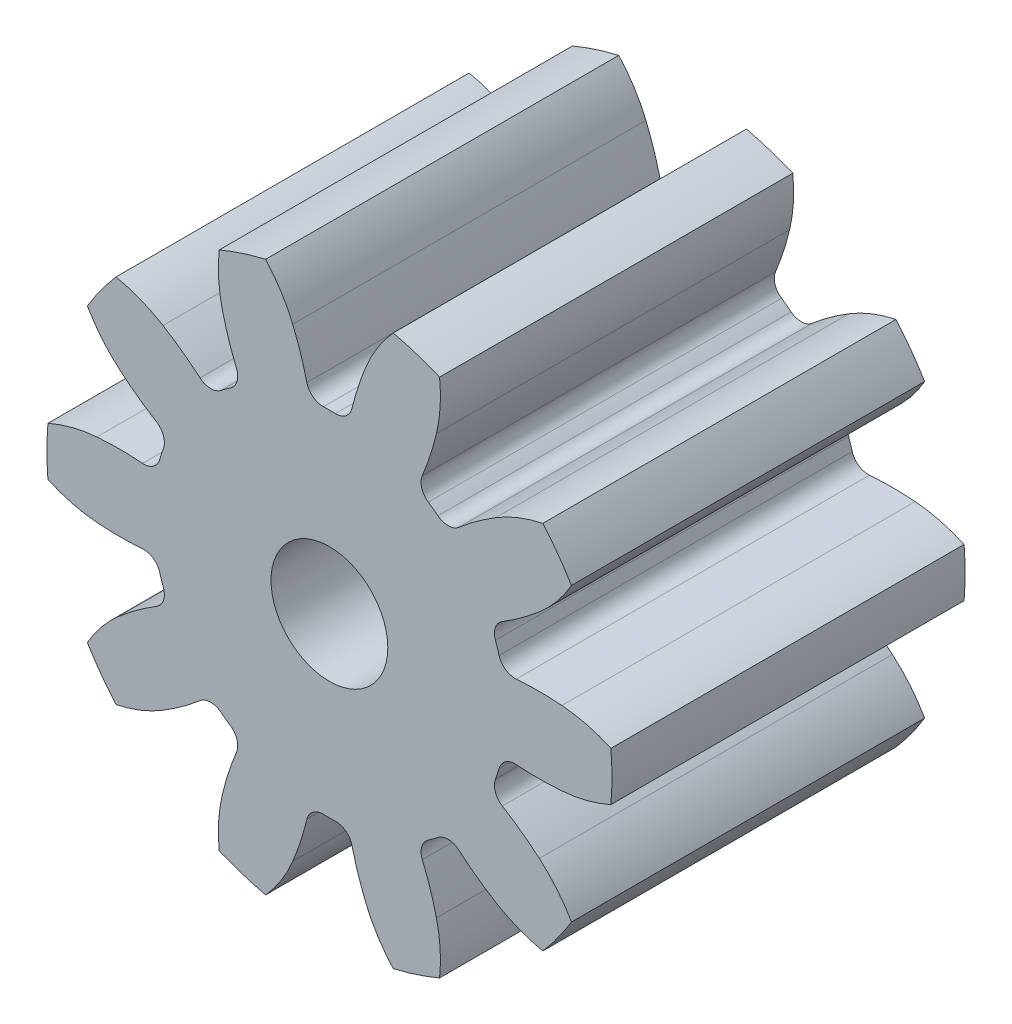
SolidWorks part; units mm, degrees
material "Alum Plate"
ref_plane "Front" through (0, 0, 0) normal (0, 0, 1) x (1, 0, 0)
ref_plane "Top" through (0, 0, 0) normal (0, 1, 0) x (1, 0, 0)
ref_plane "Right" through (0, 0, 0) normal (1, 0, 0) x (0, 0, -1)
sketch "Sketch1" plane through (0, 0, 0) normal (0, 0, 1) x (1, 0, 0)
  line L0 (0, 0) -> (6.35, 0) construction
  line L1 (6.35, 0) -> (7.62, 0) construction
  circle A0 centre (0, 0) radius 6.35 construction
  circle A1 centre (0, 0) radius 7.62
  dimension "D1" = 12.7
  dimension "D2" = 1.27
extrude "Round Stock" add sketch "Sketch1" along normal mid plane 9.525
sketch "Sketch2" plane through (0, 0, 4.7625) normal (0, 0, 1) x (1, 0, 0)
  line L0 (0, 0) -> (4.7625, 0) construction
  line L1 (4.7625, 0) -> (6.35, 0) construction
  line L2 (0, 0) -> (-7.62, 0) construction
  line L3 (0, 0) -> (-6.1647, -4.4789) construction
  line L4 (-6.5279, -3.9307) -> (-5.6598, -2.879) construction
  line L5 (-5.6598, -2.879) -> (-4.3534, -1.9312) construction
  line L6 (-7.5916, -0.657) -> (-6.2712, -0.9976) construction
  line L7 (-6.2712, -0.9976) -> (-4.6571, -0.9965) construction
  line L8 (-5.0735, -3.6861) -> (-5.6598, -2.879) construction
  line L9 (-6.2712, -0.9976) -> (-6.2712, 0) construction
  line L12 (0, 0) -> (-6.2712, -0.9976) construction
  line L13 (0, 0) -> (-5.6598, -2.879) construction
  line L14 (-5.6598, -2.879) -> (-3.7501, -6.6333) construction
  line L15 (-6.2712, -0.9976) -> (-6.9329, 3.1622) construction
  line L16 (-5.6598, -2.879) -> (-6.2712, -0.9976) construction
  line L17 (-4.5294, -1.4717) -> (-4.6571, -0.9965) construction
  line L18 (-4.5294, -1.4717) -> (-4.3534, -1.9312) construction
  circle A0 centre (0, 0) radius 6.35 construction
  circle A1 centre (0, 0) radius 4.7625 construction
  circle A2 centre (0, 0) radius 7.62 construction
  arc A3 (-6.5279, -3.9307) -> (-7.5916, -0.657) centre (0, 0) cw
  arc A4 (-4.3534, -1.9312) -> (-4.6571, -0.9965) centre (0, 0) cw construction
  arc A6 (-6.5279, -3.9307) -> (-5.6598, -2.879) centre (-3.0618, -5.9077) cw
  arc A7 (-7.5916, -0.657) -> (-6.2712, -0.9976) centre (-5.9495, 2.9798) ccw
  arc A8 (-5.6598, -2.879) -> (-4.6633, -2.1543) centre (-0.6549, -8.7137) cw
  arc A9 (-6.2712, -0.9976) -> (-5.039, -0.9981) centre (-5.6516, 6.6646) ccw
  arc A10 (-4.6633, -2.1543) -> (-4.4772, -1.6235) centre (-4.8951, -1.775) ccw
  arc A11 (-5.039, -0.9981) -> (-4.5764, -1.3182) centre (-5.0036, -1.4412) cw
  arc A12 (-4.4772, -1.6235) -> (-4.5764, -1.3182) centre (0, 0) cw
  dimension "D6" = 12.7
  dimension "D9" = 0.4445
  dimension "D12" = 3.9903
  dimension "D2" = 1.5875
  dimension "D3" = 36
  dimension "D4" = 0.9976
  dimension "D5" = 0.9976
  dimension "D11" = 1.9783
  dimension "D8" = 14.5
  dimension "D7" = 14.5
  dimension "D14" = 9
  dimension "D15" = 9
extrude "Single Tooth" cut sketch "Sketch2" against normal through all
ref_axis "Axis" through (0, 0, 50) along (0, 0, -1)
pattern_circular "Tooth Pattern" count 10 over 360 about axis through (0, 0, 50) along (0, 0, -1) of "Single Tooth"
sketch "Sketch5" plane through (0, 0, 4.7625) normal (0, 0, 1) x (1, 0, 0)
  circle A0 centre (0, 0) radius 1.5748
  dimension "D1" = 3.1496
extrude "Cut-Extrude1" cut sketch "Sketch5" against normal through all
equation "\"N_teeth\"= \"No_Teeth\""
equation "\"pitch_diameter\"= \"N_teeth\" / \"Pitch\""
equation "\"Pd\"=\"N_teeth\"/\"pitch_diameter\""
equation "\"addendum\"=1.000/\"Pd\""
equation "\"face_width\"=0.375000"
equation "\"deddendum\"=1.250/\"Pd\""
equation "\"D3@Sketch2\" = 360/\"N_teeth\""
equation "\"tooth_thickness\"=1.571/\"Pd\""
equation "\"D4@Sketch2\" = \"tooth_thickness\"/2"
equation "\"D5@Sketch2\" = \"tooth_thickness\"/2"
equation "\"Pressure_Angle\"= iif ( \"Pitch\" = 20 , 14.500000 , iif ( \"Pitch\" = 32 , 20 , 20 ) )"
equation "\"base_fillet\"=0.35/\"Pd\""
equation "\"D12@Sketch2\" = 2*\"tooth_thickness\""
equation "\"hub_projection\"=0.250000"
equation "\"sss_diam\"= 0.062500"
equation "\"D1@Sketch1\"=\"pitch_diameter\""
equation "\"D2@Sketch1\"=\"addendum\""
equation "\"D1@Round Stock\" = \"face_width\""
equation "\"D2@Sketch2\"=\"deddendum\""
equation "\"D6@Sketch2\"=\"pitch_diameter\""
equation "\"D7@Sketch2\"=\"Pressure_Angle\""
equation "\"D8@Sketch2\"=\"D7@Sketch2\""
equation "\"D9@Sketch2\"=\"base_fillet\""
equation "\"D1@Tooth Pattern\" = \"N_teeth\""
equation "\"Pitch\"= \"GearPitch\""
equation "\"BossDia\"= \"BoreDia\" * 1.3"
equation "\"Hex\"= iif ( \"HexBore\" = 1 , \"unsuppressed\" , \"suppressed\" )"
equation "\"TopBearingBoss\" = iif ( \"Bearing_Boss\" = 0 , \"suppressed\" , \"unsuppressed\" )"
equation "\"BottomBearingBoss\"= iif ( \"Bearing_Boss\" > 1 , \"unsuppressed\" , \"suppressed\" )"
equation "\"D1@Sketch4\"=\"BossDia\""
equation "\"D1@Sketch7\"=\"BossDia\"/2+.01"
equation "\"ToothCount\"= iif ( \"No_Teeth\" < 22 , \"suppressed\" , \"unsuppressed\" )"
